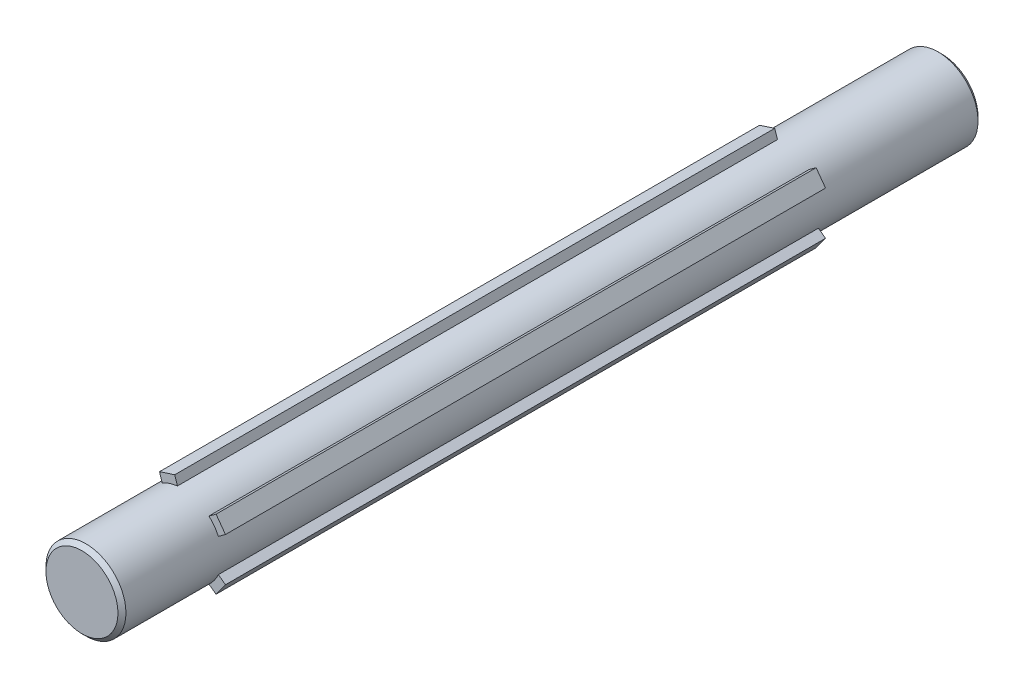
SolidWorks part; units mm, degrees
ref_plane "Front Plane" through (0, 0, 0) normal (0, 0, 1) x (1, 0, 0)
ref_plane "Top Plane" through (0, 0, 0) normal (0, 1, 0) x (1, 0, 0)
ref_plane "Right Plane" through (0, 0, 0) normal (1, 0, 0) x (0, 0, -1)
sketch "Sketch1" plane through (0, 0, 0) normal (0, 0, 1) x (1, 0, 0)
  line L0 (-5.6103, 10.7946) -> (-4.3742, 6.9904)
  line L1 (-12, 2) -> (-8, 2)
  line L2 (-12, 2) -> (-12, -2)
  line L3 (-12, -2) -> (-8, -2)
  line L4 (-8, 2) -> (-8, -2)
  line L5 (-12, 2) -> (-8, -2) construction
  line L6 (-12, -2) -> (-8, 2) construction
  line L7 (-1.8061, 12.0307) -> (-5.6103, 10.7946)
  line L8 (-1.8061, 12.0307) -> (-0.57, 8.2265)
  line L9 (-0.57, 8.2265) -> (-4.3742, 6.9904)
  line L10 (8.5326, 8.6715) -> (5.2966, 6.3203)
  line L11 (10.8838, 5.4354) -> (8.5326, 8.6715)
  line L12 (10.8838, 5.4354) -> (7.6477, 3.0842)
  line L13 (7.6477, 3.0842) -> (5.2966, 6.3203)
  line L14 (10.8838, -5.4354) -> (7.6477, -3.0842)
  line L15 (8.5326, -8.6715) -> (10.8838, -5.4354)
  line L16 (8.5326, -8.6715) -> (5.2966, -6.3203)
  line L17 (5.2966, -6.3203) -> (7.6477, -3.0842)
  line L18 (-1.8061, -12.0307) -> (-0.57, -8.2265)
  line L19 (-5.6103, -10.7946) -> (-1.8061, -12.0307)
  line L20 (-5.6103, -10.7946) -> (-4.3742, -6.9904)
  line L21 (-4.3742, -6.9904) -> (-0.57, -8.2265)
  circle A0 centre (0, 0) radius 10
  point P3 (-10, 0)
  point P27 (0, 0)
  dimension "D1" = 20
  dimension "D2" = 4
  dimension "D3" = 4
  dimension "D4" = 5
extrude "Boss-Extrude1" add sketch "Sketch1" along normal blind 215 contours L10 A0 L8 L9 L0 L1 L4 L3 L20 L21 L18 L16 L17 L14 L12 L13 | L8 A0 L0 L9 | L12 A0 L10 L13 | L1 A0 L3 L4 | L20 A0 L18 L21 | L16 A0 L14 L17 region at (-2.7711, 8.5285, 0) region at (0, 0, 0) region at (-8.9674, 0, 0) region at (7.2548, 5.2709, 0) region at (-2.7711, -8.5285, 0) region at (7.2548, -5.2709, 0)
extrude "Boss-Extrude2" add sketch "Sketch1<3>" along normal blind 150 from offset 40 contours A0 L12 L11 L10 | A0 L16 L15 L14 | A0 L8 L7 L0 | A0 L1 L2 L3 | A0 L20 L19 L18 region at (-3.3886, 10.4289, 0) region at (-10.9656, 0, 0) region at (8.8713, 6.4454, 0) region at (-3.3886, -10.4289, 0) region at (8.8713, -6.4454, 0)
sketch "Sketch1<3>" plane through (0, 0, 0) normal (0, 0, 1) x (1, 0, 0) same geometry as "Sketch1"
chamfer "Chamfer1" distance 1 angle 45 2 edges at (10, 0, 215) (10, 0, 0)
